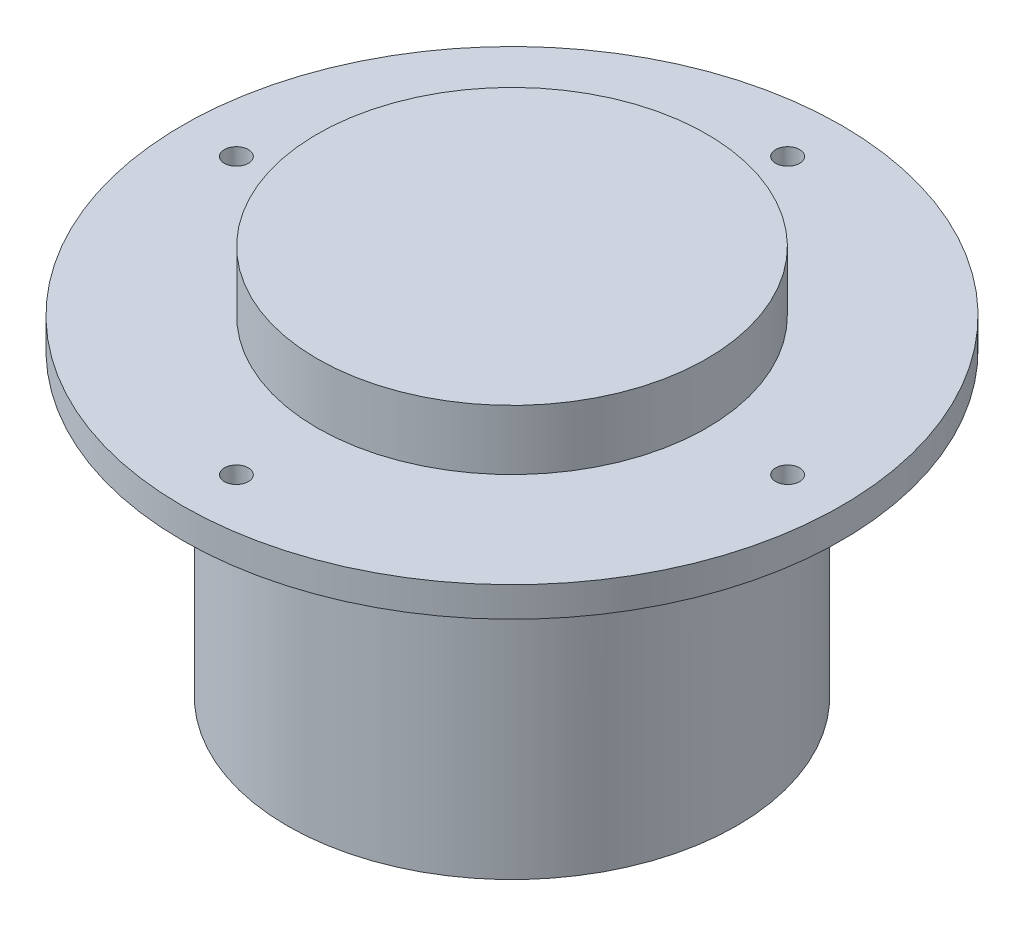
SolidWorks part; units mm, degrees
ref_plane "Front Plane" through (0, 0, 0) normal (0, 0, 1) x (1, 0, 0)
ref_plane "Top Plane" through (0, 0, 0) normal (0, 1, 0) x (1, 0, 0)
ref_plane "Right Plane" through (0, 0, 0) normal (1, 0, 0) x (0, 0, -1)
sketch "Sketch1" plane through (0, 0, 0) normal (0, 1, 0) x (1, 0, 0)
  circle A0 centre (0, 0) radius 32.5
  circle A1 centre (0, 0) radius 55
  circle A2 centre (0, 46) radius 2
  dimension "D1" = 65
  dimension "D2" = 110
  dimension "D3" = 4
  dimension "D4" = 46
extrude "Boss-Extrude1" add sketch "Sketch1" along normal blind 5 contours A0 | A1 A2 A0 region at (0, 0, 0) region at (-53.4444, 0, 0)
sketch "Sketch3" plane through (0, 0, 0) normal (0, -1, 0) x (1, 0, 0)
  circle A0 centre (0, 0) radius 37.5
  circle A2 centre (0, 0) radius 32.5
  dimension "D1" = 75
extrude "Boss-Extrude3" add sketch "Sketch3" along normal blind 50 contours A2 | A0 region at (0, 0, 0)
extrude "Boss-Extrude4" add sketch "Sketch1<4>" along normal blind 15 contours A0
sketch "Sketch1<4>" plane through (0, 0, 0) normal (0, 1, 0) x (1, 0, 0) same geometry as "Sketch1"
pattern_circular "CirPattern1" count 4 every 90 about axis through (0, 15, 0) along (0, 1, 0) of face at (0, 5, -44)
